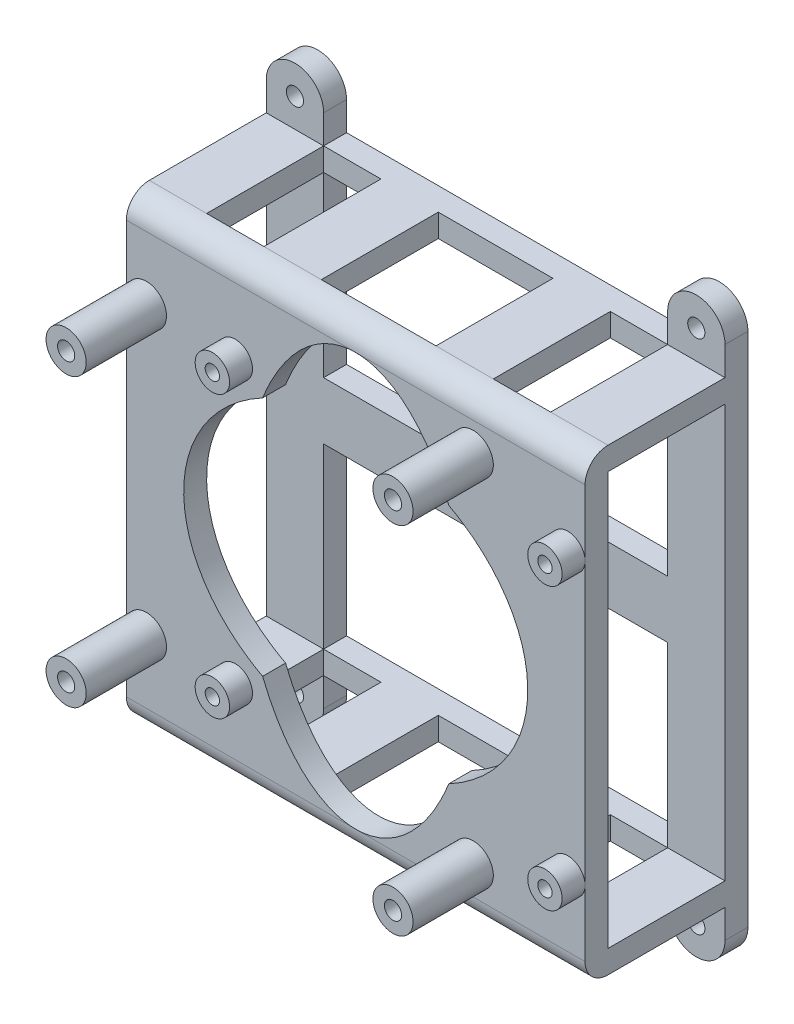
SolidWorks part; units mm, degrees
ref_plane "Alzado" through (0, 0, 0) normal (0, 0, 1) x (1, 0, 0)
ref_plane "Planta" through (0, 0, 0) normal (0, 1, 0) x (1, 0, 0)
ref_plane "Vista lateral" through (0, 0, 0) normal (1, 0, 0) x (0, 0, -1)
sketch "Croquis1" plane through (0, 0, 0) normal (0, 0, 1) x (1, 0, 0)
  line L0 (-50.9465, -21.9298) -> (-50.9465, -17.9298) construction
  line L1 (-50.9465, 58.0702) -> (29.0535, 58.0702)
  line L2 (-50.9465, 58.0702) -> (-50.9465, -21.9298)
  line L3 (-50.9465, -21.9298) -> (29.0535, -21.9298)
  line L4 (29.0535, 58.0702) -> (29.0535, -21.9298)
  line L5 (-50.9465, 58.0702) -> (-50.9465, 54.0702) construction
  line L6 (29.0535, -21.9298) -> (19.0535, -21.9298) construction
  line L7 (-50.9465, -17.9298) -> (29.0535, -17.9298)
  line L8 (-50.9465, -17.9298) -> (-50.9465, -21.9298)
  line L9 (-50.9465, -21.9298) -> (29.0535, -21.9298)
  line L10 (29.0535, -17.9298) -> (29.0535, -21.9298)
  line L11 (-50.9465, 54.0702) -> (29.0535, 54.0702)
  line L12 (-50.9465, 54.0702) -> (-50.9465, 58.0702)
  line L13 (-50.9465, 58.0702) -> (29.0535, 58.0702)
  line L14 (29.0535, 54.0702) -> (29.0535, 58.0702)
  line L15 (-50.9465, -21.9298) -> (-40.9465, -21.9298) construction
  line L16 (-50.9465, 18.0702) -> (29.0535, 18.0702) construction
  line L17 (29.0535, -21.9298) -> (19.0535, -21.9298)
  line L18 (29.0535, -21.9298) -> (29.0535, 58.0702)
  line L19 (29.0535, 58.0702) -> (19.0535, 58.0702)
  line L20 (19.0535, -21.9298) -> (19.0535, 58.0702)
  line L21 (-50.9465, 58.0702) -> (-40.9465, 58.0702)
  line L22 (-50.9465, 58.0702) -> (-50.9465, -21.9298)
  line L23 (-50.9465, -21.9298) -> (-40.9465, -21.9298)
  line L24 (-40.9465, 58.0702) -> (-40.9465, -21.9298)
  line L29 (19.0535, -21.9298) -> (9.5535, -21.9298) construction
  line L30 (29.0535, 18.0702) -> (29.0535, -6.4298) construction
  line L31 (29.0535, 18.0702) -> (29.0535, 42.5702) construction
  line L32 (29.0535, 42.5702) -> (-50.9465, 42.5702) construction
  line L33 (29.0535, -6.4298) -> (-50.9465, -6.4298) construction
  line L34 (29.0535, -6.4298) -> (26.0535, -6.4298) construction
  line L35 (-50.9465, 18.0702) -> (-50.9465, 43.0702) construction
  line L36 (-50.9465, 18.0702) -> (-50.9465, -6.9298) construction
  line L37 (-50.9465, 18.0702) -> (-50.9465, 49.0702) construction
  line L38 (-50.9465, 18.0702) -> (-50.9465, -12.9298) construction
  line L39 (-50.9465, 49.0702) -> (29.0535, 49.0702) construction
  line L40 (-50.9465, -12.9298) -> (29.0535, -12.9298) construction
  line L41 (9.5535, -21.9298) -> (9.5535, 58.0702) construction
  line L42 (9.5535, -12.9298) -> (-47.4465, -12.9298) construction
  line L43 (-47.4465, -21.9298) -> (-47.4465, 58.0702) construction
  line L44 (26.0535, -21.9298) -> (26.0535, 58.0702) construction
  line L45 (-50.9465, 43.0702) -> (29.0535, 43.0702) construction
  line L46 (-50.9465, -6.9298) -> (29.0535, -6.9298) construction
  line L47 (26.0535, -6.4298) -> (-31.9465, -6.4298) construction
  line L48 (-40.9465, 58.0702) -> (-40.9465, 68.0702) construction
  line L49 (-40.9465, -21.9298) -> (-40.9465, -31.9298) construction
  line L50 (-50.9465, -21.9298) -> (-40.9465, -31.9298) construction
  line L51 (-50.9465, -21.9298) -> (-40.9465, -21.9298)
  line L52 (-50.9465, -21.9298) -> (-50.9465, -31.9298)
  line L53 (-50.9465, -31.9298) -> (-40.9465, -31.9298)
  line L54 (-40.9465, -21.9298) -> (-40.9465, -31.9298)
  line L55 (19.0535, -21.9298) -> (29.0535, -21.9298)
  line L56 (19.0535, -21.9298) -> (19.0535, -31.9298)
  line L57 (19.0535, -31.9298) -> (29.0535, -31.9298)
  line L58 (29.0535, -21.9298) -> (29.0535, -31.9298)
  line L59 (-50.9465, 58.0702) -> (-40.9465, 58.0702)
  line L60 (-50.9465, 58.0702) -> (-50.9465, 68.0702)
  line L61 (-50.9465, 68.0702) -> (-40.9465, 68.0702)
  line L62 (-40.9465, 58.0702) -> (-40.9465, 68.0702)
  line L63 (19.0535, 58.0702) -> (29.0535, 58.0702)
  line L64 (19.0535, 58.0702) -> (19.0535, 68.0702)
  line L65 (19.0535, 68.0702) -> (29.0535, 68.0702)
  line L66 (29.0535, 58.0702) -> (29.0535, 68.0702)
  line L67 (-50.9465, -31.9298) -> (-40.9465, -21.9298) construction
  line L68 (19.0535, -21.9298) -> (29.0535, -31.9298) construction
  line L69 (19.0535, -31.9298) -> (29.0535, -21.9298) construction
  line L70 (19.0535, 68.0702) -> (29.0535, 58.0702) construction
  line L71 (29.0535, 68.0702) -> (19.0535, 58.0702) construction
  line L72 (-50.9465, 58.0702) -> (-40.9465, 68.0702) construction
  line L73 (-40.9465, 58.0702) -> (-50.9465, 68.0702) construction
  line L74 (-10.9465, 58.0702) -> (-10.9465, -21.9298)
  line L75 (-30.9465, 58.0702) -> (-30.9465, -21.9298)
  line L76 (9.0535, 58.0702) -> (9.0535, -21.9298)
  line L77 (-20.9465, 58.0702) -> (-20.9465, -21.9298)
  line L78 (-0.9465, 58.0702) -> (-0.9465, -21.9298)
  line L79 (-50.9465, 13.0702) -> (29.0535, 13.0702)
  line L80 (-50.9465, 23.0702) -> (29.0535, 23.0702)
  line L82 (-50.9465, 13.0702) -> (29.0535, 13.0702)
  line L83 (-50.9465, 13.0702) -> (-50.9465, 23.0702)
  line L84 (-50.9465, 23.0702) -> (29.0535, 23.0702)
  line L85 (29.0535, 13.0702) -> (29.0535, 23.0702)
  line L86 (-50.9465, -21.9298) -> (29.0535, -21.9298)
  line L87 (-50.9465, -21.9298) -> (-50.9465, -17.9298)
  line L88 (-50.9465, -17.9298) -> (29.0535, -17.9298)
  line L89 (29.0535, -21.9298) -> (29.0535, -17.9298)
  line L90 (-50.9465, 54.0702) -> (29.0535, 54.0702)
  line L91 (-50.9465, 54.0702) -> (-50.9465, 58.0702)
  line L92 (-50.9465, 58.0702) -> (29.0535, 58.0702)
  line L93 (29.0535, 54.0702) -> (29.0535, 58.0702)
  circle A0 centre (9.5535, -12.9298) radius 3.5
  circle A1 centre (9.5535, 49.0702) radius 3.5
  circle A2 centre (9.5535, 49.0702) radius 1.5
  circle A3 centre (9.5535, -12.9298) radius 1.5
  circle A4 centre (9.5535, 49.0702) radius 2.2
  circle A5 centre (9.5535, -12.9298) radius 2.2
  circle A12 centre (26.0535, 42.5702) radius 3
  circle A13 centre (26.0535, -6.4298) radius 3
  circle A14 centre (-47.4465, 43.0702) radius 3.5
  circle A15 centre (-47.4465, 43.0702) radius 2.2
  circle A16 centre (-47.4465, 43.0702) radius 1.5
  circle A17 centre (-47.4465, -6.9298) radius 3.5
  circle A18 centre (-47.4465, -6.9298) radius 2.2
  circle A19 centre (-47.4465, -6.9298) radius 1.5
  circle A20 centre (26.0535, -6.4298) radius 1.25
  circle A21 centre (26.0535, 42.5702) radius 1.25
  circle A22 centre (-31.9465, -6.4298) radius 3
  circle A23 centre (-31.9465, -6.4298) radius 1.25
  circle A24 centre (-31.9465, 42.5702) radius 3
  circle A25 centre (-31.9465, 42.5702) radius 1.25
  circle A26 centre (-45.9465, 63.0702) radius 1.5
  circle A27 centre (24.0535, 63.0702) radius 1.5
  circle A28 centre (24.0535, -26.9298) radius 1.5
  circle A29 centre (-45.9465, -26.9298) radius 1.5
  dimension "D15" = 57
  dimension "D16" = 58
  dimension "D19" = 20
  dimension "D1" = 80
  dimension "D2" = 80
  dimension "D3" = 4
  dimension "D4" = 4
  dimension "D5" = 10
  dimension "D6" = 10
  dimension "D7" = 9.5
  dimension "D8" = 24.5
  dimension "D9" = 24.5
  dimension "D10" = 3
  dimension "D11" = 25
  dimension "D12" = 25
  dimension "D13" = 31
  dimension "D14" = 31
  dimension "D20" = 20
  dimension "D21" = 10
  dimension "D22" = 10
  dimension "D23" = 5
  dimension "D24" = 5
extrude "Saliente-Extruir5" add sketch "Croquis1" along normal blind 4 contours L1 L62 L61 L60 A26 | L13 L66 L65 L64 A27 | L58 L9 L56 L57 A28 | L54 L3 L52 L53 A29 | L24 L7 L2 L3 | L75 L7 L24 L9 | L77 L7 L75 L3 | L7 L77 L9 L74 | L78 L7 L74 L3 | L7 L78 L9 L76 | L7 L76 L9 L20 | L20 L9 L4 L7 | A13 A20 | A20 | L4 A13 L18 L79 L20 L7 | L22 A17 L2 L7 L24 L79 | A17 A18 | A18 A19 | A19 | L80 L22 L79 L24 | L80 L24 L79 L75 | L80 L75 L79 L77 | L80 L77 L79 L74 | L80 L74 L79 L78 | L80 L78 L79 L76 | L80 L76 L79 L20 | L80 L20 L79 L18 | L2 A14 L22 L80 L24 L11 | L24 L1 L2 L11 | A14 A15 | A15 A16 | A16 | L75 L13 L24 L11 | L77 L1 L75 L11 | L13 L77 L11 L74 | L78 L1 L74 L11 | L13 L78 L11 L76 | L13 L76 L11 L20 | L20 L11 L4 L13 | L18 A12 L4 L11 L20 L80 | A12 A21 | A21 region at (-50.8051, 63.0702, 0) region at (-45.9465, 56.0702, 0) region at (-35.9465, 56.0702, 0) region at (-47.4465, 46.4712, 0) region at (-45.7339, 37.9323, 0) region at (-25.9465, 56.0702, 0) region at (-15.9465, 56.0702, 0) region at (-35.9465, 18.0702, 0) region at (-45.9465, 18.0702, 0) region at (-5.9465, 56.0702, 0) region at (-47.4465, -3.5288, 0) region at (-45.7339, -1.792, 0) region at (-25.9465, 18.0702, 0) region at (4.0535, 56.0702, 0) region at (-15.9465, 18.0702, 0) region at (-45.9465, -19.9298, 0) region at (-35.9465, -19.9298, 0) region at (14.0535, 56.0702, 0) region at (-5.9465, 18.0702, 0) region at (-25.9465, -19.9298, 0) region at (-41.0879, -26.9298, 0) region at (19.1949, 63.0702, 0) region at (24.0535, 56.0702, 0) region at (4.0535, 18.0702, 0) region at (-15.9465, -19.9298, 0) region at (23.1383, 42.5702, 0) region at (23.8528, 38.1687, 0) region at (14.0535, 18.0702, 0) region at (-5.9465, -19.9298, 0) region at (24.0535, 18.0702, 0) region at (4.0535, -19.9298, 0) region at (23.1383, -6.4298, 0) region at (23.8528, -2.0284, 0) region at (14.0535, -19.9298, 0) region at (24.0535, -19.9298, 0) region at (24.0535, -22.0712, 0) region at (-49.5843, 43.0702, 0) region at (-47.4465, 43.0702, 0) region at (-49.5843, -6.9298, 0) region at (-47.4465, -6.9298, 0) region at (26.0535, -6.4298, 0) region at (26.0535, 42.5702, 0)
extrude "Saliente-Extruir6" add sketch "Croquis1<6>" along normal blind 20.4 from surface contours L24 L1 L2 L11 | L77 L1 L75 L11 | L20 L11 L4 L13 | L13 L78 L11 L76 | L24 L7 L2 L3 | L77 L7 L75 L3 | L7 L78 L9 L76 | L20 L9 L4 L7 region at (-45.9465, 56.0702, 0) region at (-25.9465, 56.0702, 0) region at (4.0535, 56.0702, 0) region at (-45.9465, -19.9298, 0) region at (-25.9465, -19.9298, 0) region at (24.0535, 56.0702, 0) region at (4.0535, -19.9298, 0) region at (24.0535, -19.9298, 0) starting at face at (-10.9465, -2.4298, 4)
sketch "Croquis1<6>" plane through (0, 0, 0) normal (0, 0, 1) x (1, 0, 0) same geometry as "Croquis1"
extrude "Saliente-Extruir7" add sketch "Croquis1<7>" along normal blind 4 from surface contours L24 L1 L2 L11 | L75 L13 L24 L11 | L13 L77 L11 L74 | L78 L1 L74 L11 | L13 L78 L11 L76 | L77 L1 L75 L11 | L13 L76 L11 L20 | L18 A12 L4 L11 L20 L80 | L2 A14 L22 L80 L24 L11 | A24 L75 L11 L24 L80 | A14 A15 | A15 A16 | A16 | A12 A21 | A21 | L20 L11 L4 L13 | A25 L75 A24 | L75 A25 | A25 L75 A24 | L75 A25 | A24 L75 L80 L77 L11 | L77 L80 L74 L11 | L74 L80 L78 L11 | A1 L76 L11 L78 L80 | A4 L76 A1 | L76 A4 A2 | L76 A2 | L76 A2 | L76 A4 A2 | A4 L76 A1 | A1 L76 L80 L20 L11 | L80 L20 L79 L18 | L80 L76 L79 L20 | L80 L78 L79 L76 | L80 L74 L79 L78 | L80 L77 L79 L74 | L80 L75 L79 L77 | L80 L24 L79 L75 | L80 L22 L79 L24 | A22 L75 L79 L24 L7 | A22 L75 L7 L77 L79 | L79 L77 L7 L74 | L79 L74 L7 L78 | A0 L76 L79 L78 L7 | A0 L76 L7 L20 L79 | L22 A17 L2 L7 L24 L79 | A17 A18 | A18 A19 | A19 | A23 L75 A22 | L75 A23 | L75 A23 | A23 L75 A22 | A13 A20 | A20 | L76 A3 | L76 A3 | L76 A5 A3 | A5 L76 A0 | L76 A5 A3 | A5 L76 A0 | L20 L9 L4 L7 | L7 L76 L9 L20 | L7 L78 L9 L76 | L78 L7 L74 L3 | L7 L77 L9 L74 | L77 L7 L75 L3 | L75 L7 L24 L9 | L24 L7 L2 L3 | L4 A13 L18 L79 L20 L7 region at (-45.9465, 56.0702, 0) region at (-35.9465, 56.0702, 0) region at (-47.4465, 46.4712, 0) region at (-45.7339, 37.9323, 0) region at (-25.9465, 56.0702, 0) region at (-36.1707, 38.294, 0) region at (-15.9465, 56.0702, 0) region at (-25.8325, 38.4608, 0) region at (-35.9465, 18.0702, 0) region at (-45.9465, 18.0702, 0) region at (-5.9465, 56.0702, 0) region at (-15.9465, 38.5702, 0) region at (-30.0948, 42.5702, 0) region at (-31.0186, 44.3594, 0) region at (-36.1707, -2.1536, 0) region at (-47.4465, -3.5288, 0) region at (-45.7339, -1.792, 0) region at (-25.9465, 18.0702, 0) region at (4.0535, 56.0702, 0) region at (-5.9465, 38.5702, 0) region at (-15.9465, 18.0702, 0) region at (-30.8456, 42.5702, 0) region at (-32.007, 42.5702, 0) region at (-45.9465, -19.9298, 0) region at (-35.9465, -19.9298, 0) region at (-25.8325, -2.3205, 0) region at (14.0535, 56.0702, 0) region at (3.8532, 38.008, 0) region at (-5.9465, 18.0702, 0) region at (-15.9465, -2.4298, 0) region at (-25.9465, -19.9298, 0) region at (-30.0948, -6.4298, 0) region at (-31.0186, -4.6406, 0) region at (24.0535, 56.0702, 0) region at (14.3131, 37.7394, 0) region at (4.0535, 18.0702, 0) region at (-5.9465, -2.4298, 0) region at (-15.9465, -19.9298, 0) region at (-30.8456, -6.4298, 0) region at (-32.007, -6.4298, 0) region at (23.1383, 42.5702, 0) region at (23.8528, 38.1687, 0) region at (11.792, 51.655, 0) region at (8.978, 51.8734, 0) region at (3.8532, -1.8676, 0) region at (14.0535, 18.0702, 0) region at (-5.9465, -19.9298, 0) region at (24.0535, 18.0702, 0) region at (10.8889, 50.7531, 0) region at (9.0074, 50.8485, 0) region at (4.0535, -19.9298, 0) region at (14.3131, -1.599, 0) region at (23.1383, -6.4298, 0) region at (23.8528, -2.0284, 0) region at (9.9301, 49.0702, 0) region at (8.6393, 49.0702, 0) region at (14.0535, -19.9298, 0) region at (11.792, -10.345, 0) region at (8.978, -10.1266, 0) region at (24.0535, -19.9298, 0)
sketch "Croquis1<7>" plane through (0, 0, 0) normal (0, 0, 1) x (1, 0, 0) same geometry as "Croquis1"
extrude "Saliente-Extruir9" add sketch "Croquis1<10>" along normal blind 4 from surface contours A24 | A12 | A13 | A22 starting at face at (-10.9465, 18.0702, 28.4)
sketch "Croquis1<10>" plane through (0, 0, 0) normal (0, 0, 1) x (1, 0, 0) same geometry as "Croquis1"
extrude "Saliente-Extruir10" add sketch "Croquis1<11>" along normal blind 14 from surface contours A14 | A17 | A0 | A1 starting at face at (-34.9465, -6.4298, 28.4)
sketch "Croquis1<11>" plane through (0, 0, 0) normal (0, 0, 1) x (1, 0, 0) same geometry as "Croquis1"
extrude "Cortar-Extruir1" cut sketch "Croquis1<12>" against normal blind 14 and the other way blind 14 from surface contours A19 | A23 | A3 | A20 | A21 | A2 | A25 | A16 starting at face at (6.0535, 49.0702, 28.4)
sketch "Croquis1<12>" plane through (0, 0, 0) normal (0, 0, 1) x (1, 0, 0) same geometry as "Croquis1"
extrude "Cortar-Extruir2" cut sketch "Croquis1<13>" along normal blind 15 from surface contours A5 | A18 | A15 | A4 starting at face at (-33.1965, -6.4298, 24.4)
sketch "Croquis1<13>" plane through (0, 0, 0) normal (0, 0, 1) x (1, 0, 0) same geometry as "Croquis1"
fillet "Redondeo2" 2 edges at (-40.9465, 68.0702, 2) (-50.9465, 68.0702, 2) type full round first side face at (-40.9465, 63.0702, 2) second side face at (-50.9465, 18.0702, 12.96) middle face at (-45.9465, 68.0702, 2)
fillet "Redondeo3" 2 edges at (-50.9465, -31.9298, 2) (-40.9465, -31.9298, 2) type full round first side face at (-50.9465, 17.0702, 12.96) second side face at (-40.9465, -26.9298, 2) middle face at (-45.9465, -31.9298, 2)
fillet "Redondeo4" 2 edges at (19.0535, -31.9298, 2) (29.0535, -31.9298, 2) type full round first side face at (19.0535, -26.9298, 2) second side face at (29.0535, 18.0702, 12.96) middle face at (24.0535, -31.9298, 2)
fillet "Redondeo5" 2 edges at (19.0535, 68.0702, 2) (29.0535, 68.0702, 2) type full round first side face at (19.0535, 63.0702, 2) second side face at (29.0535, 19.0702, 12.96) middle face at (24.0535, 68.0702, 2)
sketch "Croquis2" plane through (0, 0, 0) normal (0, 0, 1) x (1, 0, 0)
  line L0 (-50.9465, -21.9298) -> (-50.9465, -17.9298) construction
  line L1 (-50.9465, 58.0702) -> (29.0535, 58.0702)
  line L2 (-50.9465, 58.0702) -> (-50.9465, -21.9298)
  line L3 (-50.9465, -21.9298) -> (29.0535, -21.9298)
  line L4 (29.0535, 58.0702) -> (29.0535, -21.9298)
  line L5 (-50.9465, 58.0702) -> (-50.9465, 54.0702) construction
  line L6 (29.0535, -21.9298) -> (19.0535, -21.9298) construction
  line L7 (-50.9465, -17.9298) -> (29.0535, -17.9298)
  line L8 (-50.9465, -17.9298) -> (-50.9465, -21.9298)
  line L9 (-50.9465, -21.9298) -> (29.0535, -21.9298)
  line L10 (29.0535, -17.9298) -> (29.0535, -21.9298)
  line L11 (-50.9465, 54.0702) -> (29.0535, 54.0702)
  line L12 (-50.9465, 54.0702) -> (-50.9465, 58.0702)
  line L13 (-50.9465, 58.0702) -> (29.0535, 58.0702)
  line L14 (29.0535, 54.0702) -> (29.0535, 58.0702)
  line L15 (-50.9465, -21.9298) -> (-40.9465, -21.9298) construction
  line L16 (-50.9465, 18.0702) -> (29.0535, 18.0702) construction
  line L17 (29.0535, -21.9298) -> (19.0535, -21.9298)
  line L18 (29.0535, -21.9298) -> (29.0535, 58.0702)
  line L19 (29.0535, 58.0702) -> (19.0535, 58.0702)
  line L20 (19.0535, -21.9298) -> (19.0535, 58.0702)
  line L21 (-50.9465, 58.0702) -> (-40.9465, 58.0702)
  line L22 (-50.9465, 58.0702) -> (-50.9465, -21.9298)
  line L23 (-50.9465, -21.9298) -> (-40.9465, -21.9298)
  line L24 (-40.9465, 58.0702) -> (-40.9465, -21.9298)
  line L29 (19.0535, -21.9298) -> (9.5535, -21.9298) construction
  line L30 (29.0535, 18.0702) -> (29.0535, -6.4298) construction
  line L31 (29.0535, 18.0702) -> (29.0535, 42.5702) construction
  line L32 (29.0535, 42.5702) -> (-50.9465, 42.5702) construction
  line L33 (29.0535, -6.4298) -> (-50.9465, -6.4298) construction
  line L34 (29.0535, -6.4298) -> (26.0535, -6.4298) construction
  line L35 (-50.9465, 18.0702) -> (-50.9465, 43.0702) construction
  line L36 (-50.9465, 18.0702) -> (-50.9465, -6.9298) construction
  line L37 (-50.9465, 18.0702) -> (-50.9465, 49.0702) construction
  line L38 (-50.9465, 18.0702) -> (-50.9465, -12.9298) construction
  line L39 (-50.9465, 49.0702) -> (29.0535, 49.0702) construction
  line L40 (-50.9465, -12.9298) -> (29.0535, -12.9298) construction
  line L41 (9.5535, -21.9298) -> (9.5535, 58.0702) construction
  line L42 (9.5535, -12.9298) -> (-47.4465, -12.9298) construction
  line L43 (-47.4465, -21.9298) -> (-47.4465, 58.0702) construction
  line L44 (26.0535, -21.9298) -> (26.0535, 58.0702) construction
  line L45 (-50.9465, 43.0702) -> (29.0535, 43.0702) construction
  line L46 (-50.9465, -6.9298) -> (29.0535, -6.9298) construction
  line L47 (26.0535, -6.4298) -> (-31.9465, -6.4298) construction
  line L48 (-40.9465, 58.0702) -> (-40.9465, 68.0702) construction
  line L49 (-40.9465, -21.9298) -> (-40.9465, -31.9298) construction
  line L50 (-50.9465, -21.9298) -> (-40.9465, -31.9298) construction
  line L51 (-50.9465, -21.9298) -> (-40.9465, -21.9298)
  line L52 (-50.9465, -21.9298) -> (-50.9465, -31.9298)
  line L53 (-50.9465, -31.9298) -> (-40.9465, -31.9298)
  line L54 (-40.9465, -21.9298) -> (-40.9465, -31.9298)
  line L55 (19.0535, -21.9298) -> (29.0535, -21.9298)
  line L56 (19.0535, -21.9298) -> (19.0535, -31.9298)
  line L57 (19.0535, -31.9298) -> (29.0535, -31.9298)
  line L58 (29.0535, -21.9298) -> (29.0535, -31.9298)
  line L59 (-50.9465, 58.0702) -> (-40.9465, 58.0702)
  line L60 (-50.9465, 58.0702) -> (-50.9465, 68.0702)
  line L61 (-50.9465, 68.0702) -> (-40.9465, 68.0702)
  line L62 (-40.9465, 58.0702) -> (-40.9465, 68.0702)
  line L63 (19.0535, 58.0702) -> (29.0535, 58.0702)
  line L64 (19.0535, 58.0702) -> (19.0535, 68.0702)
  line L65 (19.0535, 68.0702) -> (29.0535, 68.0702)
  line L66 (29.0535, 58.0702) -> (29.0535, 68.0702)
  line L67 (-50.9465, -31.9298) -> (-40.9465, -21.9298) construction
  line L68 (19.0535, -21.9298) -> (29.0535, -31.9298) construction
  line L69 (19.0535, -31.9298) -> (29.0535, -21.9298) construction
  line L70 (19.0535, 68.0702) -> (29.0535, 58.0702) construction
  line L71 (29.0535, 68.0702) -> (19.0535, 58.0702) construction
  line L72 (-50.9465, 58.0702) -> (-40.9465, 68.0702) construction
  line L73 (-40.9465, 58.0702) -> (-50.9465, 68.0702) construction
  line L74 (-10.9465, 58.0702) -> (-10.9465, -21.9298)
  line L75 (-30.9465, 58.0702) -> (-30.9465, -21.9298)
  line L76 (9.0535, 58.0702) -> (9.0535, -21.9298)
  line L77 (-20.9465, 58.0702) -> (-20.9465, -21.9298)
  line L78 (-0.9465, 58.0702) -> (-0.9465, -21.9298)
  line L79 (-50.9465, 13.0702) -> (29.0535, 13.0702)
  line L80 (-50.9465, 23.0702) -> (29.0535, 23.0702)
  line L82 (-50.9465, 13.0702) -> (29.0535, 13.0702)
  line L83 (-50.9465, 13.0702) -> (-50.9465, 23.0702)
  line L84 (-50.9465, 23.0702) -> (29.0535, 23.0702)
  line L85 (29.0535, 13.0702) -> (29.0535, 23.0702)
  line L86 (-50.9465, -21.9298) -> (29.0535, -21.9298)
  line L87 (-50.9465, -21.9298) -> (-50.9465, -17.9298)
  line L88 (-50.9465, -17.9298) -> (29.0535, -17.9298)
  line L89 (29.0535, -21.9298) -> (29.0535, -17.9298)
  line L90 (-50.9465, 54.0702) -> (29.0535, 54.0702)
  line L91 (-50.9465, 54.0702) -> (-50.9465, 58.0702)
  line L92 (-50.9465, 58.0702) -> (29.0535, 58.0702)
  line L93 (29.0535, 54.0702) -> (29.0535, 58.0702)
  circle A0 centre (9.5535, -12.9298) radius 3.5
  circle A1 centre (9.5535, 49.0702) radius 3.5
  circle A2 centre (9.5535, 49.0702) radius 1.5
  circle A3 centre (9.5535, -12.9298) radius 1.5
  circle A4 centre (9.5535, 49.0702) radius 2.2
  circle A5 centre (9.5535, -12.9298) radius 2.2
  circle A12 centre (26.0535, 42.5702) radius 3
  circle A13 centre (26.0535, -6.4298) radius 3
  circle A14 centre (-47.4465, 43.0702) radius 3.5
  circle A15 centre (-47.4465, 43.0702) radius 2.2
  circle A16 centre (-47.4465, 43.0702) radius 1.5
  circle A17 centre (-47.4465, -6.9298) radius 3.5
  circle A18 centre (-47.4465, -6.9298) radius 2.2
  circle A19 centre (-47.4465, -6.9298) radius 1.5
  circle A20 centre (26.0535, -6.4298) radius 1.25
  circle A21 centre (26.0535, 42.5702) radius 1.25
  circle A22 centre (-31.9465, -6.4298) radius 3
  circle A23 centre (-31.9465, -6.4298) radius 1.25
  circle A24 centre (-31.9465, 42.5702) radius 3
  circle A25 centre (-31.9465, 42.5702) radius 1.25
  circle A26 centre (-45.9465, 63.0702) radius 1.5
  circle A27 centre (24.0535, 63.0702) radius 1.5
  circle A28 centre (24.0535, -26.9298) radius 1.5
  circle A29 centre (-45.9465, -26.9298) radius 1.5
  ellipse E0 centre (-10.9465, 18.0702) end of major axis (-40.9465, 18.0702) minor radius 25
  ellipse E1 centre (-10.9465, 18.0702) end of major axis (-10.9465, -17.9298) minor radius 20
  dimension "D15" = 57
  dimension "D16" = 58
  dimension "D19" = 20
  dimension "D1" = 80
  dimension "D2" = 80
  dimension "D3" = 4
  dimension "D4" = 4
  dimension "D5" = 10
  dimension "D6" = 10
  dimension "D7" = 9.5
  dimension "D8" = 24.5
  dimension "D9" = 24.5
  dimension "D10" = 3
  dimension "D11" = 25
  dimension "D12" = 25
  dimension "D13" = 31
  dimension "D14" = 31
  dimension "D20" = 20
  dimension "D21" = 10
  dimension "D22" = 10
  dimension "D23" = 5
  dimension "D24" = 5
fillet "Redondeo6" radius 4 1 edges at (-10.9465, -21.9298, 28.4) type face fillet first side face at (-10.9465, -21.9298, 11.65) second side face at (6.0535, 49.0702, 28.4)
fillet "Redondeo7" radius 4 1 edges at (-10.9465, 58.0702, 28.4) type face fillet first side face at (-10.9465, 58.0702, 11.65) second side face at (6.0535, 49.0702, 28.4)
extrude "Cortar-Extruir6" cut sketch "Croquis2" against normal blind 8 from surface contours E1 | E0 starting at face at (6.0535, 49.0702, 28.4)
